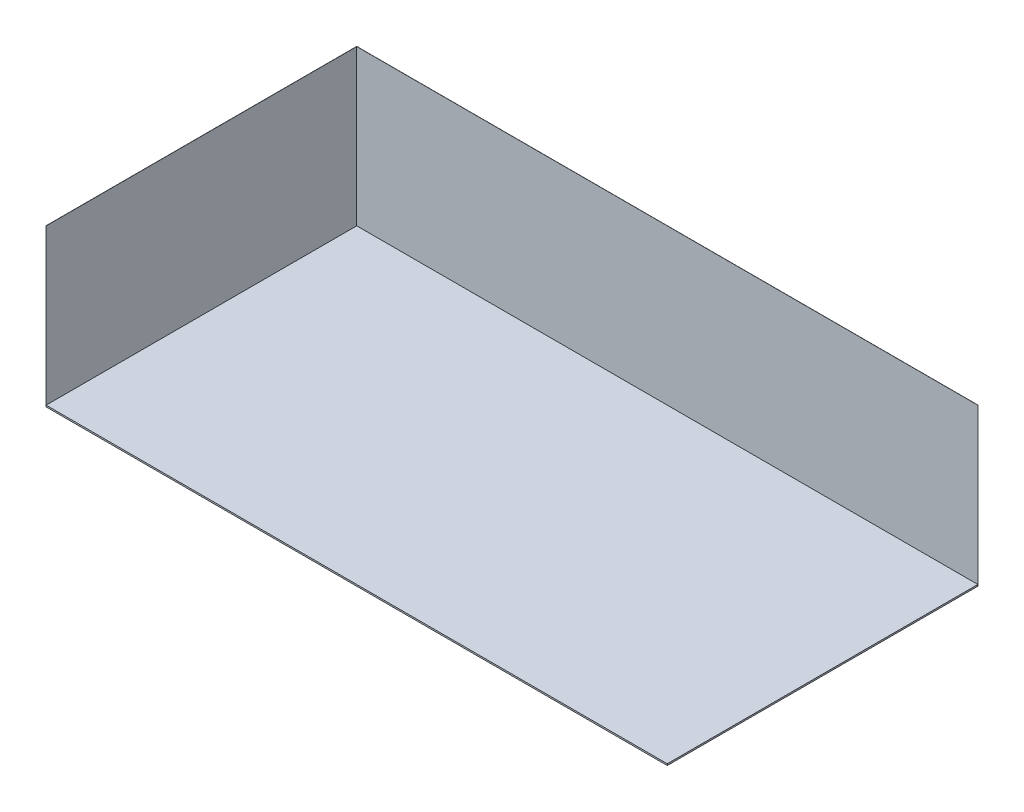
SolidWorks part; units mm, degrees
ref_plane "Front Plane" through (0, 0, 0) normal (0, 0, 1) x (1, 0, 0)
ref_plane "Top Plane" through (0, 0, 0) normal (0, 1, 0) x (1, 0, 0)
ref_plane "Right Plane" through (0, 0, 0) normal (1, 0, 0) x (0, 0, -1)
sketch "Sketch2" plane through (0, 0, 0) normal (0, 1, 0) x (1, 0, 0)
  line L1 (-53.3201, 19.4977) -> (48.2799, 19.4977)
  line L2 (-53.3201, 19.4977) -> (-53.3201, -31.3023)
  line L3 (-53.3201, -31.3023) -> (48.2799, -31.3023)
  line L4 (48.2799, 19.4977) -> (48.2799, -31.3023)
  dimension "Length_Floor" = 101.6
  dimension "Width_Floor" = 50.8
extrude "Floor" add sketch "Sketch2" along normal blind 0.254
sketch "Sketch3" plane through (0, 0.254, 0) normal (0, 1, 0) x (1, 0, 0)
  line L0 (48.2799, 19.4977) -> (-53.3201, 19.4977) construction
  line L1 (48.2799, 19.4977) -> (-53.3201, 19.4977)
extrude "Wall1" add sketch "Sketch3" along normal blind 25.4 separate body thin thin type one direction wall 0.0254
sketch "Sketch4" plane through (0, 0.254, 0) normal (0, 1, 0) x (1, 0, 0)
  line L0 (-53.3201, 19.4977) -> (-53.3201, -31.3023) construction
  line L1 (-53.3201, 19.4977) -> (-53.3201, -31.3023)
extrude "Wall2" add sketch "Sketch4" along normal blind 25.4 separate body thin thin type one direction wall 0.0254
